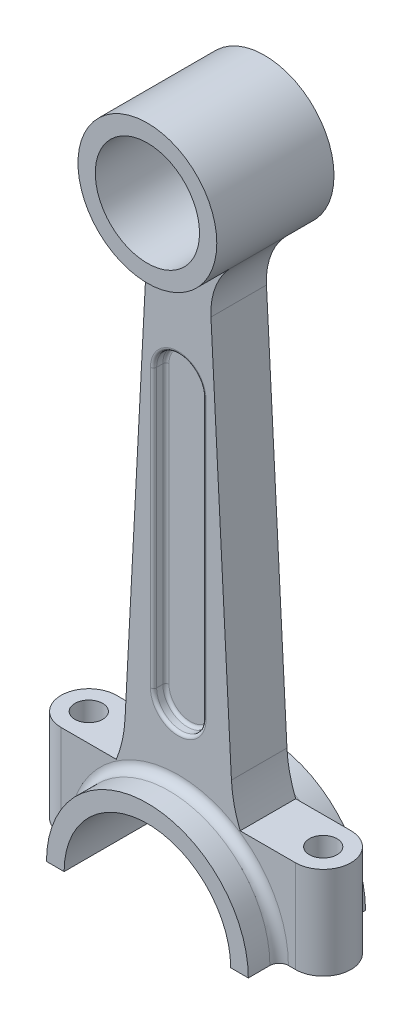
SolidWorks part; units mm, degrees
ref_plane "Front Plane" through (0, 0, 0) normal (0, 0, 1) x (1, 0, 0)
ref_plane "Top Plane" through (0, 0, 0) normal (0, 1, 0) x (1, 0, 0)
ref_plane "Right Plane" through (0, 0, 0) normal (1, 0, 0) x (0, 0, -1)
sketch "Sketch1" plane through (0, 0, 0) normal (0, 0, 1) x (1, 0, 0)
  line L0 (0, 0) -> (0, -201.2) construction
  line L1 (-10, -20.1556) -> (-18.0581, -173.9131)
  line L2 (10, -20.1556) -> (18.0581, -173.9131)
  line L3 (-32.7211, -201.2) -> (-27, -201.2)
  line L4 (27, -201.2) -> (32.7211, -201.2)
  circle A0 centre (0, 0) radius 22.5
  circle A1 centre (0, 0) radius 16.9
  arc A2 (27, -201.2) -> (-27, -201.2) centre (0, -201.2) ccw
  arc A3 (32.7211, -201.2) -> (-32.7211, -201.2) centre (0, -201.2) ccw
  dimension "D1" = 45
  dimension "D2" = 201.2
  dimension "33.8" = 33.8
  dimension "D3" = 20
  dimension "D4" = 6
extrude "Boss-Extrude4" add sketch "Sketch1" along normal mid plane 38 contours A3 A2 | A1 A0 | L3 A2 L4 A3 region at (-11.5231, 18.5805, 0) region at (0, -169.2106, 0)
extrude "Boss-Extrude5" add sketch "Sketch1<6>" along normal mid plane 18 contours A0 L0 A3 L2 | L0 A0 L1 A3 region at (7.2448, -102.8673, 0) region at (-7.2448, -102.8673, 0)
sketch "Sketch1<6>" plane through (0, 0, 0) normal (0, 0, 1) x (1, 0, 0) same geometry as "Sketch1"
sketch "Sketch3" plane through (0, 0, 9) normal (0, 0, 1) x (1, 0, 0)
  line L0 (0, 0) -> (0, -201.2) construction
  line L1 (0, -145.6) -> (0, -55.6) construction
  line L2 (-8, -145.6) -> (-8, -55.6)
  line L3 (8, -145.6) -> (8, -55.6)
  arc A0 (-8, -145.6) -> (8, -145.6) centre (0, -145.6) ccw
  arc A1 (8, -55.6) -> (-8, -55.6) centre (0, -55.6) ccw
  point P6 (0, -100.6)
  dimension "D2" = 8
  dimension "D1" = 90
extrude "Cut-Extrude1" cut sketch "Sketch3" against normal blind 4
mirror "Mirror1" about plane through (0, 0, 0) normal (0, 0, 1) of "Cut-Extrude1"
fillet "Fillet1" radius 1 16 edges at (0, -47.6, 9) (8, -100.6, 9) (0, -153.6, 9) (0, -153.6, -5) (-8, -100.6, -5) (0, -47.6, -5) (0, -153.6, -9) (-8, -100.6, -9) (0, -47.6, -9) (8, -100.6, 5) (0, -153.6, 5) (-8, -100.6, 5) (-8, -100.6, 9) (8, -100.6, -5) (8, -100.6, -9) (0, -47.6, 5)
fillet "Fillet2" radius 40 2 edges at (18.0581, -173.9131, 0) (-18.0581, -173.9131, 0)
fillet "Fillet3" radius 22.5 2 edges at (10, -20.1556, 0) (-10, -20.1556, 0)
ref_plane "Plane1" through (0, -171.2, 0) normal (0, 1, 0) x (1, 0, 0)
sketch "Sketch11" plane through (0, -171.2, 0) normal (0, 1, 0) x (1, 0, 0)
  line L0 (-38, 0) -> (38, 0) construction
  line L1 (-38, 9) -> (38, 9)
  line L2 (-38, -9) -> (38, -9)
  arc A0 (-38, 9) -> (-38, -9) centre (-38, 0) ccw
  arc A1 (38, -9) -> (38, 9) centre (38, 0) ccw
  point P2 (0, 0)
  dimension "D2" = 9
  dimension "D1" = 76
extrude "Boss-Extrude6" add sketch "Sketch11" against normal up to surface (30 mm away) up to face at (-29.8606, -201.2, 0)
sketch "Sketch12" plane through (0, 0, 9) normal (0, 0, 1) x (1, 0, 0)
  line L1 (-27, -201.2) -> (27, -201.2)
  line L2 (-27, -201.2) -> (27, -201.2)
  arc A1 (27, -201.2) -> (-27, -201.2) centre (0, -201.2) ccw
  arc A2 (27, -201.2) -> (-27, -201.2) centre (0, -201.2) ccw
  dimension "D1" = 0
extrude "Cut-Extrude2" cut sketch "Sketch12" against normal through all both and the other way through all contours L2 A2
sketch "Sketch13" plane through (0, -171.2, 0) normal (0, 1, 0) x (1, 0, 0)
  circle A0 centre (-38, 0) radius 4.5
  circle A1 centre (38, 0) radius 4.5
  dimension "D1" = 9
  dimension "D2" = 9
extrude "Cut-Extrude3" cut sketch "Sketch13" against normal through all both and the other way through all contours A1 | A0
fillet "Fillet4" radius 3 2 edges at (0, -168.4789, -9) (0, -168.4789, 9)
